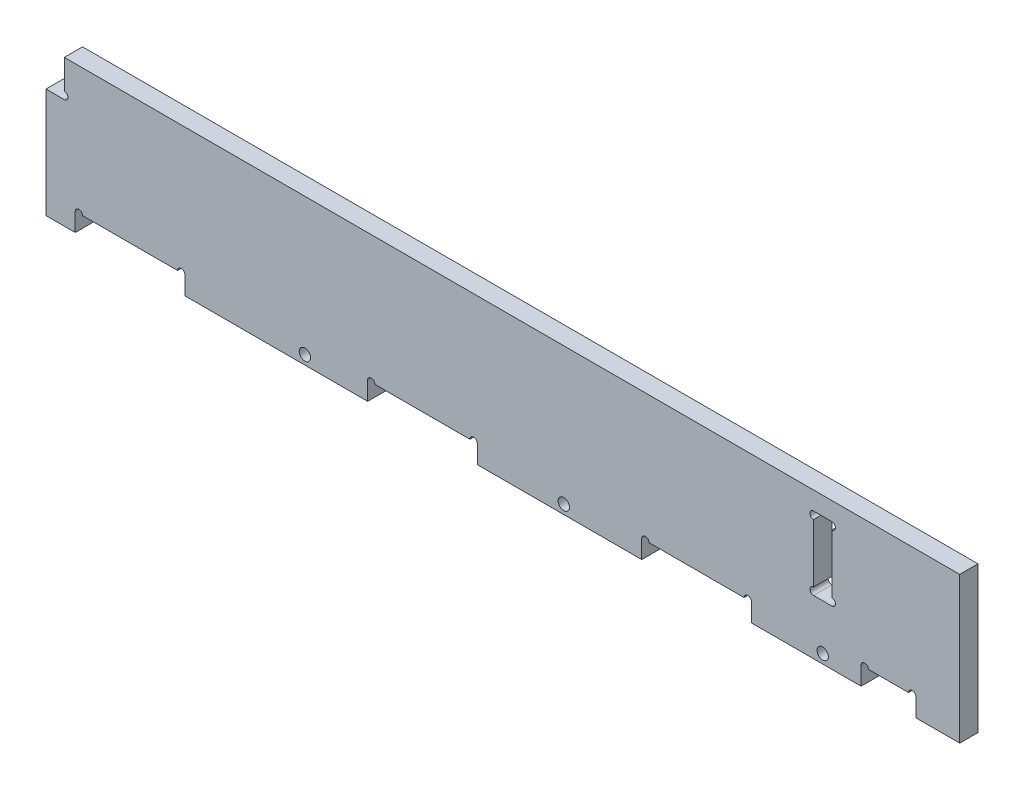
SolidWorks part; units mm, degrees
ref_plane "정면" through (0, 0, 0) normal (0, 0, 1) x (1, 0, 0)
ref_plane "윗면" through (0, 0, 0) normal (0, 1, 0) x (1, 0, 0)
ref_plane "우측면" through (0, 0, 0) normal (1, 0, 0) x (0, 0, -1)
sketch "스케치1" plane through (0, 0, 0) normal (0, 0, 1) x (1, 0, 0)
  line L1 (0, 0) -> (250, 0)
  line L2 (0, 0) -> (0, 40)
  line L3 (0, 40) -> (250, 40)
  line L4 (250, 0) -> (250, 40)
  dimension "D1" = 40
extrude "보스-돌출1" add sketch "스케치1" along normal blind 5
sketch "스케치2" plane through (0, 0, 5) normal (0, 0, 1) x (1, 0, 0)
  line L0 (0, 40) -> (0, 0) construction
  line L1 (5, 40) -> (0, 40)
  line L2 (5, 40) -> (5, 30)
  line L3 (5, 30) -> (0, 30)
  line L4 (0, 40) -> (0, 30)
  line L5 (5, 30) -> (0, 30) construction
  line L6 (0, 0) -> (250, 0) construction
  line L7 (8, 5) -> (38, 5)
  line L8 (8, 5) -> (8, 0)
  line L9 (8, 0) -> (38, 0)
  line L10 (38, 5) -> (38, 0)
  line L11 (38, 5) -> (38, 0) construction
  line L12 (118, 5) -> (118, 0) construction
  line L13 (118, 0) -> (88, 0)
  line L14 (118, 0) -> (118, 5)
  line L15 (118, 5) -> (88, 5)
  line L16 (88, 0) -> (88, 5)
  line L17 (193, 5) -> (193, 0) construction
  line L18 (193, 0) -> (163, 0)
  line L19 (193, 0) -> (193, 5)
  line L20 (193, 5) -> (163, 5)
  line L21 (163, 0) -> (163, 5)
  line L22 (238, 5) -> (238, 0) construction
  line L23 (238, 0) -> (223, 0)
  line L24 (238, 0) -> (238, 5)
  line L25 (238, 5) -> (223, 5)
  line L26 (223, 0) -> (223, 5)
  line L28 (210, 35) -> (215, 35)
  line L29 (210, 35) -> (210, 15)
  line L30 (210, 15) -> (215, 15)
  line L31 (215, 35) -> (215, 15)
extrude "컷-돌출1" cut sketch "스케치2" against normal blind 5
sketch "스케치3" plane through (0, 0, 5) normal (0, 0, 1) x (1, 0, 0)
  line L0 (238, 5) -> (223, 5) construction
  line L1 (215, 15) -> (215, 35) construction
  line L2 (210, 35) -> (210, 15) construction
  line L4 (193, 5) -> (163, 5) construction
  line L5 (38, 5) -> (8, 5) construction
  line L6 (118, 5) -> (88, 5) construction
  line L7 (5, 30) -> (5, 40) construction
  circle A0 centre (237, 5) radius 1
  circle A1 centre (224, 5) radius 1
  circle A2 centre (210, 16) radius 1
  circle A3 centre (215, 16) radius 1
  circle A4 centre (215, 34) radius 1
  circle A5 centre (210, 34) radius 1
  circle A6 centre (164, 5) radius 1
  circle A7 centre (192, 5) radius 1
  circle A8 centre (37, 5) radius 1
  circle A9 centre (89, 5) radius 1
  circle A10 centre (117, 5) radius 1
  circle A11 centre (5, 31) radius 1
  circle A13 centre (9, 5) radius 1
  dimension "D1" = 2
  dimension "D2" = 2
extrude "컷-돌출2" cut sketch "스케치3" against normal blind 5
sketch "스케치4" plane through (0, 0, 0) normal (0, 0, -1) x (-1, 0, 0)
  line L0 (-72.3833, 2.5) -> (-69.2833, 2.5) construction
  line L1 (-72.3833, 5) -> (-72.3833, 0) construction
  line L2 (-69.2833, 5) -> (-69.2833, 0) construction
  line L3 (-143.2167, 2.5) -> (-140.1167, 2.5) construction
  line L4 (-143.2167, 5) -> (-143.2167, 0) construction
  line L5 (-140.1167, 5) -> (-140.1167, 0) construction
  line L6 (-214.05, 2.5) -> (-210.95, 2.5) construction
  line L7 (-214.05, 5) -> (-214.05, 0) construction
  line L8 (-210.95, 5) -> (-210.95, 0) construction
  circle A0 centre (-212.5, 2.5) radius 1.55
  circle A1 centre (-141.6667, 2.5) radius 1.55
  circle A2 centre (-70.8333, 2.5) radius 1.55
extrude "컷-돌출3" cut sketch "스케치4" against normal blind 10
